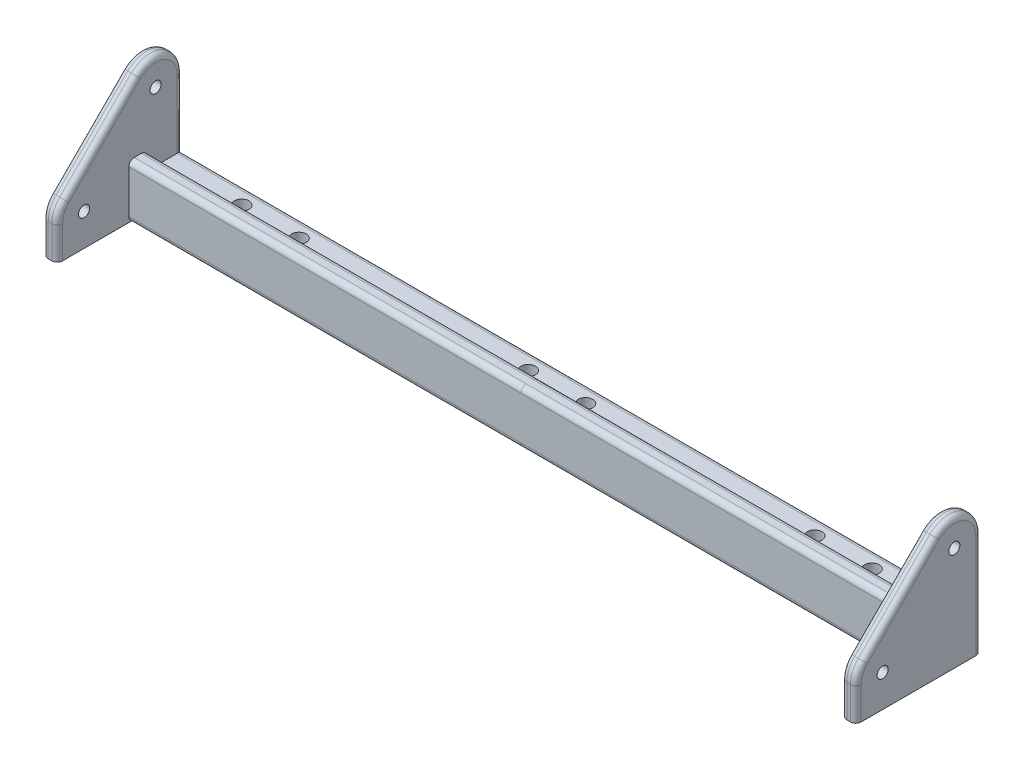
SolidWorks part; units mm, degrees
ref_plane "Plan de face" through (0, 0, 0) normal (0, 0, 1) x (1, 0, 0)
ref_plane "Plan de dessus" through (0, 0, 0) normal (0, 1, 0) x (1, 0, 0)
ref_plane "Plan de droite" through (0, 0, 0) normal (1, 0, 0) x (0, 0, -1)
sketch "Esquisse1" plane through (0, 0, 0) normal (0, 0, 1) x (1, 0, 0)
  line L0 (0, 0) -> (0, 44.2701) construction
  line L1 (0, 0) -> (122.3999, 0) construction
  line L2 (0, 5) -> (122.3999, 5) construction
  line L3 (0, 10) -> (122.3999, 10) construction
  line L4 (0, 0) -> (0, 5) construction
  line L5 (0, 5) -> (15, 5) construction
  line L6 (15, 5) -> (15, 10) construction
  line L7 (15, 10) -> (65, 10) construction
  line L8 (65, 10) -> (65, 5) construction
  line L9 (65, 5) -> (95, 5) construction
  line L10 (95, 5) -> (95, 10) construction
  line L11 (95, 10) -> (109.5, 10) construction
  line L12 (109.5, 10) -> (109.5, 0) construction
  line L13 (109.5, 0) -> (0, 0) construction
  line L14 (80, 5) -> (80, 10) construction
  line L15 (0, 10) -> (0, 5)
  line L16 (0, 5) -> (15, 5) construction
  line L17 (15, 5) -> (15, 0) construction
  line L18 (15, 0) -> (65, 0) construction
  line L19 (65, 0) -> (65, 5) construction
  line L20 (65, 5) -> (95, 5) construction
  line L21 (95, 5) -> (95, 0) construction
  line L22 (95, 0) -> (109.5, 0) construction
  line L23 (109.5, 0) -> (109.5, 10)
  line L24 (109.5, 10) -> (0, 10)
  line L25 (0, 5) -> (0, 0)
  line L26 (0, 0) -> (109.5, 0)
  dimension "D1" = 30
  dimension "D2" = 5
  dimension "D3" = 5
  dimension "D4" = 15
  dimension "D5" = 80
  dimension "D6" = 109.5
extrude "Boss.-Extru.1" add sketch "Esquisse1" along normal blind 15
sketch "Esquisse2" plane through (109.5, 0, 0) normal (1, 0, 0) x (0, 0, -1)
  line L0 (0, 0) -> (0, 35.377) construction
  line L1 (0, 0) -> (-43.9624, 0) construction
  line L2 (-36.5, 0) -> (6.4379, 42.9379) construction
  line L3 (1.5, 0) -> (-32.0262, 33.5262) construction
  line L4 (-17.5, 19) -> (20.3247, 19) construction
  line L5 (-17.5, 9) -> (-17.5, 54.8988) construction
  line L8 (-12.8033, 34.3033) -> (-32.8033, 14.3033)
  line L9 (-35, 9) -> (-35, 0)
  line L12 (-35, 0) -> (-15, 0)
  line L13 (0, 29) -> (0, 10)
  line L14 (0, 29) -> (0, 10)
  line L24 (0, 0) -> (0, 10)
  line L25 (0, 10) -> (-15, 10)
  line L26 (-15, 10) -> (-15, 0)
  line L27 (-15, 0) -> (0, 0)
  line L28 (0, 0) -> (0, 10)
  line L29 (0, 10) -> (-15, 10)
  line L30 (-15, 10) -> (-15, 0)
  line L35 (-15, 0) -> (0, 0)
  circle A0 centre (-27.5, 9) radius 1.55
  circle A1 centre (-27.5, 9) radius 10 construction
  circle A2 centre (-7.5, 29) radius 10 construction
  circle A3 centre (-7.5, 29) radius 1.55
  circle A4 centre (-27.5, 9) radius 7.5 construction
  circle A5 centre (-7.5, 29) radius 7.5 construction
  arc A6 (-32.8033, 14.3033) -> (-35, 9) centre (-27.5, 9) ccw
  arc A7 (0, 29) -> (-12.8033, 34.3033) centre (-7.5, 29) ccw
  dimension "D1" = 45
  dimension "D3" = 3.1
  dimension "D4" = 20
  dimension "D5" = 15
  dimension "D7" = 9
  dimension "D2" = 45
  dimension "D6" = 0
extrude "Boss.-Extru.2" add sketch "Esquisse2" along normal blind 4 contours A7 L8 A6 L9 A3 A0 | L35 L28 L29 L30 region at (109.5, 16.6903, 16.1151)
sketch "Esquisse5" plane through (0, 0, 0) normal (0, -1, 0) x (1, 0, 0)
  line L0 (0, 48.5635) -> (0, -28.5102) construction
  line L1 (-30.4412, 0) -> (140.7754, 0) construction
  line L2 (-6.1805, 5) -> (139.8263, 5) construction
  line L3 (80, 19.9399) -> (80, -9.3402) construction
  line L6 (0, 0) -> (113.5, 0)
  line L7 (113.5, 0) -> (113.5, 35)
  line L8 (113.5, 35) -> (109.5, 35)
  line L9 (109.5, 35) -> (109.5, 15)
  line L10 (109.5, 15) -> (0, 15)
  line L11 (0, 15) -> (0, 0)
  line L12 (0, 0) -> (113.5, 0)
  line L13 (113.5, 0) -> (113.5, 35)
  line L14 (113.5, 35) -> (109.5, 35)
  line L15 (109.5, 35) -> (109.5, 15)
  line L16 (109.5, 15) -> (0, 15)
  line L17 (0, 15) -> (0, 0)
  circle A0 centre (8, 5) radius 2.05
  circle A1 centre (72, 5) radius 2.05
  circle A2 centre (88, 5) radius 2.05
  dimension "D2" = 8
  dimension "D5" = 4.1
  dimension "D3" = 8
  dimension "D4" = 80
  dimension "D6" = 5
  dimension "D1" = 0
extrude "Enlèv. mat.-Extru.3" cut sketch "Esquisse5" against normal through all contours A0 | A1 | A2
sketch "Esquisse7" plane through (0, 10, 0) normal (0, 1, 0) x (1, 0, 0)
  line L0 (0, -10) -> (109.5, -10)
  line L4 (109.5, 0) -> (0, 0)
  line L5 (0, 0) -> (0, -15)
  line L6 (0, -15) -> (109.5, -15)
  line L7 (109.5, -15) -> (109.5, 0)
  line L8 (109.5, 0) -> (0, 0)
  line L9 (0, 0) -> (0, -15)
  line L10 (0, -15) -> (109.5, -15)
  line L11 (109.5, -15) -> (109.5, 0)
  line M8 (0, 0) -> (0, -15)
  line M9 (0, -15) -> (109.5, -15)
  line M10 (109.5, -15) -> (109.5, 0)
  dimension "D2" = 5
  dimension "D1" = 0
extrude "Boss.-Extru.3" add sketch "Esquisse7" along normal blind 5 contours L0 M8 M9 M10 region at (54.75, 10, 12.5)
fillet "Congé1" radius 1.5 15 edges at (54.75, 10, 0) (54.75, 15, 15) (54.75, 15, 10) (54.75, 10, 10) (54.75, 0, 15) (113.5, 14.5, 0) (113.5, 35.9291, 4.6299) (113.5, 4.5, 35) (113.5, 11.8701, 34.4291) (109.5, 19.5, 0) (109.5, 35.9291, 4.6299) (109.5, 4.5, 35) (109.5, 11.8701, 34.4291) (113.5, 24.3033, 22.8033) (109.5, 24.3033, 22.8033)
mirror "Symétrie5" about plane through (0, 5, 15) normal (1, 0, 0) of "Boss.-Extru.1", "Boss.-Extru.2", "Enlèv. mat.-Extru.3", "Boss.-Extru.3", "Congé1"
